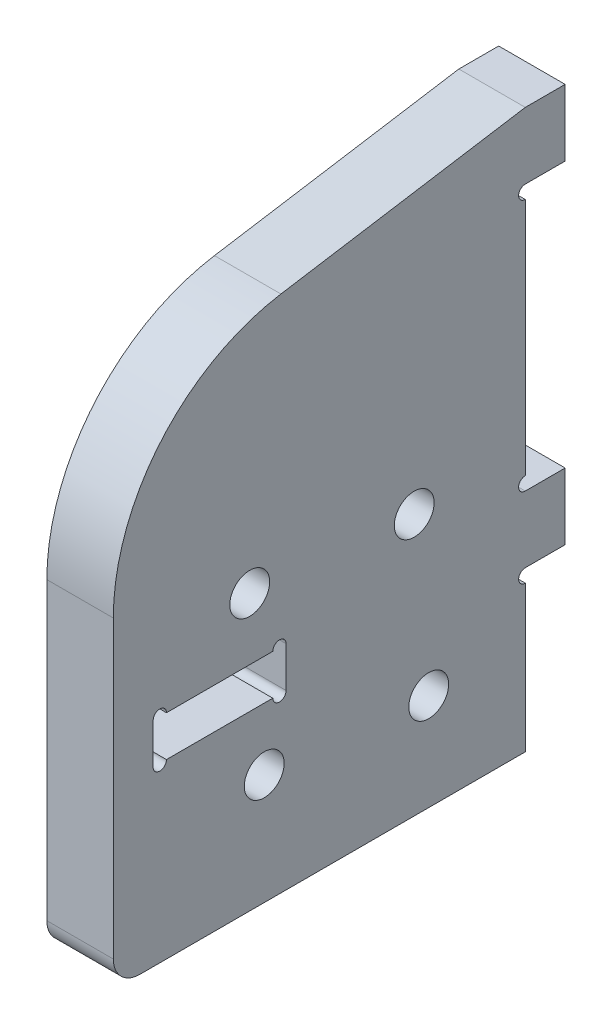
SolidWorks part; units mm, degrees
ref_plane "Front Plane" through (0, 0, 0) normal (0, 0, 1) x (1, 0, 0)
ref_plane "Top Plane" through (0, 0, 0) normal (0, 1, 0) x (1, 0, 0)
ref_plane "Right Plane" through (0, 0, 0) normal (1, 0, 0) x (0, 0, -1)
sketch "Sketch1" plane through (0, 0, 0) normal (1, 0, 0) x (0, 0, -1)
  line L0 (17, 28) -> (17, 23)
  line L1 (17, 28) -> (14, 28)
  line L2 (14, 28) -> (-17, 23)
  line L3 (-17, 23) -> (-17, -14)
  line L4 (14, -14) -> (-17, -14)
  line L6 (17, 23) -> (14, 23)
  line L7 (14, 23) -> (14, 3)
  line L8 (14, 3) -> (17, 3)
  line L9 (17, 3) -> (17, -2)
  line L10 (17, -2) -> (14, -2)
  line L11 (-6.7339, 6.7011) -> (6.7339, -6.7011) construction
  line L12 (20, 36.7745) -> (20, -39.1651) construction
  line L13 (5.643, 5.6706) -> (-5.643, -5.6706) construction
  line L14 (14, -2) -> (14, -14)
  circle A0 centre (0, 0) radius 18 construction
  circle A1 centre (-6.7339, 6.7011) radius 1.5
  circle A2 centre (-5.643, -5.6706) radius 1.5
  circle A3 centre (6.7339, -6.7011) radius 1.5
  circle A4 centre (5.643, 5.6706) radius 1.5
  dimension "D2" = 36
  dimension "D4" = 3
  dimension "D1" = 20
  dimension "D3" = 13.4022
  dimension "D5" = 5
  dimension "D6" = 3
  dimension "D7" = 17
  dimension "D8" = 14
  dimension "D9" = 12
  dimension "D10" = 28
  dimension "D11" = 17
  dimension "D12" = 5
  dimension "D13" = 5.643
  dimension "D14" = 6.7339
extrude "Boss-Extrude1" add sketch "Sketch1" along normal blind 5
sketch "Sketch2" plane through (5, 0, 0) normal (1, 0, 0) x (0, 0, -1)
  line L1 (-14, 2.05) -> (-4, 2.05)
  line L2 (-14, 2.05) -> (-14, -1)
  line L3 (-14, -1) -> (-4, -1)
  line L4 (-4, 2.05) -> (-4, -1)
  line L5 (-17, -14) -> (14, -14) construction
  line L6 (-17, 23) -> (-17, -14) construction
  dimension "D3" = 10
  dimension "D1" = 3.05
  dimension "D2" = 13
  dimension "D4" = 3
extrude "Cut-Extrude1" cut sketch "Sketch2" against normal through all
fillet "Fillet1" radius 15 1 edges at (2.5, 23, 17)
fillet "Fillet2" radius 2 1 edges at (2.5, -14, 17)
sketch "Sketch3" plane through (5, 0, 0) normal (1, 0, 0) x (0, 0, -1)
  line L0 (14, 3) -> (14, 23) construction
  line L1 (14, -14) -> (14, -2) construction
  line L2 (-4, 2.05) -> (-14, 2.05) construction
  line L3 (-14, -1) -> (-4, -1) construction
  arc A0 (14, 23) -> (14, 22) centre (14, 22.5) ccw
  arc A1 (14, 3) -> (14, 4) centre (14, 3.5) cw
  arc A2 (14, -2) -> (14, -3) centre (14, -2.5) ccw
  arc A3 (-4, 2.05) -> (-5, 2.05) centre (-4.5, 2.05) ccw
  arc A4 (-14, 2.05) -> (-13, 2.05) centre (-13.5, 2.05) cw
  arc A5 (-14, -1) -> (-13, -1) centre (-13.5, -1) ccw
  arc A6 (-4, -1) -> (-5, -1) centre (-4.5, -1) cw
  line M2 (-14, 2.05) -> (-4, 2.05)
  line M4 (-4, -1) -> (-14, -1)
  line M10 (14, -14) -> (14, -2)
  line M14 (14, 3) -> (14, 23)
  dimension "D1" = 0.5
extrude "Cut-Extrude2" cut sketch "Sketch3" against normal through all contours A4 M2 | A5 M4 | A3 M2 | A6 M4 | A1 M14 | A2 M10 | A0 M14 region at (5, 22.5, -13.7878) region at (5, 3.5, -13.7878) region at (5, -2.5, -13.7878) region at (5, 2.2622, 4.5) region at (5, 2.2622, 13.5) region at (5, -1.2122, 13.5) region at (5, -1.2122, 4.5)
